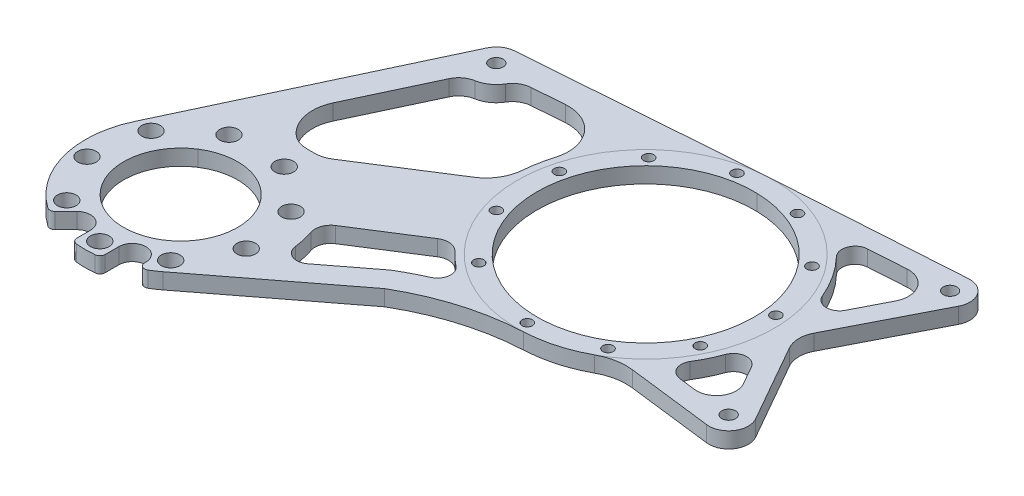
SolidWorks part; units mm, degrees
note: '?' marks a value the reader was unsure of.
other "Markup2"
sketch "Sketch8" plane through (392.176, 9.525, 205.994) normal (0, 1, 0) x (-1, 0, 0)
other "Markup3"
sketch "Sketch9" plane through (392.176, 9.525, 4.4528) normal (0, 1, 0) x (-1, 0, 0)
material "6061-T6 (SS)"
ref_plane "X-Y Datum" through (0, 0, 0) normal (0, 0, 1) x (1, 0, 0)
ref_plane "X-Z Datum" through (0, 0, 0) normal (0, 1, 0) x (1, 0, 0)
ref_plane "Y-Z Datum" through (0, 0, 0) normal (1, 0, 0) x (0, 0, -1)
sketch "Sketch1" plane through (0, 0, 0) normal (0, 1, 0) x (-1, 0, 0)
  line L1 (-575.31, 72.8215) -> (-438.15, 160.02) construction
  line L2 (-663.3443, 5.1159) -> (-571.3342, 11.0368)
  line L3 (-568.96, 0) -> (-463.042, 0) construction
  line L4 (-575.31, 72.8215) -> (-463.042, 0) construction
  line L6 (-672.4346, 18.9616) -> (-648.7868, 65.1568)
  line L8 (-414.9501, 197.3367) -> (-420.215, 192.0718)
  line L9 (-431.3112, 196.668) -> (-431.3112, 203.2407)
  line L10 (-444.9888, 203.2407) -> (-444.9888, 196.668)
  line L11 (-457.9888, 196.668) -> (-457.9888, 197.245)
  line L12 (-685.8, 0) -> (-568.96, 0) construction
  line L13 (-685.8, 130.5733) -> (-685.8, 0) construction
  line L16 (-450.7361, 24.8976) -> (-396.5254, 140.5006)
  line L17 (-670.601, 115.0847) -> (-649.0541, 77.2258)
  line L18 (-526.6297, 150.1211) -> (-466.1201, 196.5067)
  line L20 (-508.2633, 125.1657) -> (-498.3912, 109.6373) construction
  line L21 (-503.8626, 118.2436) -> (-490.7147, 118.2436) construction
  line L22 (-698.5, 155.9733) -> (-673.1, 155.9733) construction
  line L23 (-698.5, 12.7) -> (-673.1, 12.7) construction
  line L24 (-698.5, 12.7) -> (-698.5, -12.7) construction
  line L25 (-698.5, -12.7) -> (-673.1, -12.7) construction
  line L26 (-673.1, 12.7) -> (-673.1, -12.7) construction
  line L27 (-698.5, 12.7) -> (-673.1, -12.7) construction
  line L28 (-698.5, -12.7) -> (-673.1, 12.7) construction
  line L29 (-698.5, 155.9733) -> (-698.5, 130.5733) construction
  line L30 (-698.5, 130.5733) -> (-673.1, 130.5733) construction
  line L31 (-673.1, 155.9733) -> (-673.1, 130.5733) construction
  line L32 (-698.5, 155.9733) -> (-673.1, 130.5733) construction
  line L33 (-698.5, 130.5733) -> (-673.1, 155.9733) construction
  line L35 (-661.162, 129.2501) -> (-620.2745, 124.2297)
  line L36 (-672.139, 129.6123) -> (-652.5065, 109.9799) construction
  line L37 (-463.042, 0) -> (-463.042, 3.81) construction
  line L38 (-570.7022, 11.0807) -> (-458.6511, 19.4431)
  line L40 (-575.31, 125.209) -> (-575.31, 134.734) construction
  circle A3 centre (-438.15, 199.02) radius 4.5 construction
  circle A4 centre (-438.15, 160.02) radius 39 construction
  circle A5 centre (-662.3228, 119.7961) radius 9.525 construction
  circle A6 centre (-663.956, 14.6213) radius 9.525 construction
  circle A7 centre (-459.36, 28.9417) radius 9.525 construction
  circle A8 centre (-438.15, 160.02) radius 27.4955
  arc A11 (-411.6923, 197.6179) -> (-396.5254, 140.5006) centre (-438.15, 160.02) cw
  arc A13 (-672.4346, 18.9616) -> (-663.3443, 5.1159) centre (-663.956, 14.6213) ccw
  arc A16 (-461.8375, 199.4219) -> (-411.6923, 197.6179) centre (-438.15, 160.02) ccw construction
  arc A17 (-411.6923, 197.6179) -> (-414.9501, 197.3367) centre (-413.1541, 195.5407) ccw
  arc A18 (-431.3112, 196.668) -> (-420.215, 192.0718) centre (-424.8112, 196.668) ccw
  arc A19 (-431.3112, 203.2407) -> (-433.5998, 205.7683) centre (-433.8512, 203.2407) ccw
  arc A20 (-433.5998, 205.7683) -> (-442.7002, 205.7683) centre (-438.15, 160.02) ccw
  arc A21 (-442.7002, 205.7683) -> (-444.9888, 203.2407) centre (-442.4488, 203.2407) ccw
  arc A22 (-457.9888, 196.668) -> (-444.9888, 196.668) centre (-451.4888, 196.668) ccw
  arc A23 (-457.9888, 197.245) -> (-461.8375, 199.4219) centre (-460.5288, 197.245) ccw
  arc A25 (-466.1201, 196.5067) -> (-461.8375, 199.4219) centre (-438.15, 160.02) cw
  arc A27 (-526.6297, 150.1211) -> (-578.3125, 134.6611) centre (-583.7676, 247.0155) cw
  circle A38 centre (-575.31, 72.8215) radius 61.9125 construction
  circle A39 centre (-575.31, 72.8215) radius 52.3875
  arc A40 (-604.9989, 127.1513) -> (-578.3125, 134.6611) centre (-575.31, 72.8215) cw
  arc A41 (-670.601, 115.0847) -> (-661.162, 129.2501) centre (-662.3228, 119.7961) cw
  circle A42 centre (-662.3228, 119.7961) radius 3.3
  circle A43 centre (-663.956, 14.6213) radius 3.3
  circle A44 centre (-459.36, 28.9417) radius 3.3
  arc A47 (-649.0541, 77.2258) -> (-648.7868, 65.1568) centre (-660.0917, 70.9439) cw
  arc A49 (-620.2745, 124.2297) -> (-604.9989, 127.1513) centre (-617.179, 149.4404) ccw
  arc A51 (-450.7361, 24.8976) -> (-458.6511, 19.4431) centre (-459.36, 28.9417) cw
  circle A53 centre (-463.042, 3.81) radius 12.7 construction
  arc A54 (-571.3342, 11.0368) -> (-570.7022, 11.0807) centre (-575.31, 72.8215) ccw
  circle A55 centre (-685.8, 0) radius 12.7 construction
  circle A56 centre (-685.8, 1.6598) radius 12.7 construction
  circle A58 centre (-575.31, 129.9715) radius 2.5 construction
  point P71 (-685.8, 143.2733)
  point P103 (-662.3228, 119.7961)
  point P105 (-611.3847, 123.1382)
  point P112 (-611.3847, 123.1382)
  dimension "D5" = 25.4
  dimension "D6" = 685.8
  dimension "D7" = 123.825
  dimension "D8" = 104.775
  dimension "D9" = 5
  dimension "D13" = 45.974
  dimension "D14" = 19.05
  dimension "D15" = 3.81
  dimension "D16" = 117.8733
  dimension "D19" = 25.4
  dimension "D20" = 9
  dimension "D21" = 3.682
  dimension "D18" = 6.5
  dimension "D23" = 78
  dimension "D24" = 25.4
  dimension "D35" = 25.4
  dimension "D22" = 54.991
  dimension "D26" = 12.7
  dimension "D38" = 112.4868
  dimension "D41" = 6.6
  dimension "D42" = 32.446
  dimension "D43" = 21.844
  dimension "D34" = 38
  dimension "D36" = 1.6598
  dimension "D2" = 222.758
  dimension "D3" = 247.65
  dimension "D4" = 160.02
  dimension "D10" = 575.31
  dimension "D11" = 72.8215
  dimension "D12" = 116.84
  dimension "D17" = 25.4
  dimension "D25" = 22.3788
  dimension "D33" = 15.354
  dimension "D37" = 25.4
  dimension "D39" = 9.8989
  dimension "D40" = 88.4797
  dimension "D44" = 72.8215
  dimension "D46" = 10.7772
  dimension "D47" = 10.7772
extrude "Boss-Extrude1" add sketch "Sketch1" along normal mid plane 7.62
hole_wizard "M8 Clearance Hole1" positions "Sketch5" profile "Sketch4" hole size "M8" standard "ANSI Metric" end condition through all
sketch "Sketch5" plane through (0, -3.81, 0) normal (0, -1, 0) x (-1, 0, 0)
  point P0 (-438.15, -199.02)
sketch "Sketch4" plane through (438.15, -3.81, 199.02) normal (1, 0, 0) x (0, 0, -1)
  line L0 (0, 0) -> (0, 7.62)
  line L1 (0, 7.62) -> (4.5, 7.62)
  line L2 (4.5, 7.62) -> (4.5, 0.025)
  line L3 (4.5, 0.025) -> (4.525, 0)
  line L5 (4.525, 0) -> (0, 0)
  line L6 (-4.5, 0.025) -> (-4.525, 0) construction
  line L11 (0, -6.35) -> (0, 107.95) construction
  dimension "Thru Hole Dia." = 9
  dimension "Thru Hole Depth" = 7.62
  dimension "Near C'Sink Dia." = 9.05
  dimension "Near C'Sink Angle" = 90
pattern_circular "CirPattern1" count 9 over 360 about axis through (438.15, 0, 160.02) along (0, 1, 0) of "M8 Clearance Hole1"
sketch "Sketch6" plane through (0, 3.81, 0) normal (0, 1, 0) x (1, 0, 0)
  circle A0 centre (575.31, -72.8215) radius 61.9125 construction
  circle A1 centre (575.31, -72.8215) radius 61.9125
split line "Split Line2"
ref_point "Point1"
ref_point "Point2"
ref_plane "Plane1" through (570.7022, 0, 11.0807) normal (-0.8439, 0, 0.5365) x (0.5365, 0, 0.8439)
ref_plane "Plane2" through (438.15, 0, 160.02) normal (-0.8439, 0, 0.5365) x (0.5365, 0, 0.8439)
split line "Split Line3"
split line "Split Line4"
ref_axis "Axis1" through (575.31, 3.81, 72.8215) along (0, -1, 0)?
ref_axis "Axis2" through (438.15, 6.1381, 160.02) along (0, -1, 0)?
sketch "Sketch10" plane through (0, -3.81, 0) normal (0, -1, 0) x (1, 0, 0)
  line L0 (460.0554, 108.4708) -> (501.6535, 82.0251)
  line L1 (488.447, 135.5686) -> (518.5458, 116.4335)
  line L2 (462.2346, 30.2897) -> (408.0239, 145.8927)
  line L3 (454.4908, 46.8032) -> (436.5907, 84.9748)
  line L4 (449.5579, 110.4533) -> (453.2418, 110.4533)
  line L5 (575.31, 72.8215) -> (438.15, 160.02) construction
  line L9 (571.6474, 23.7455) -> (459.5963, 32.1079)
  line L13 (493.2983, 29.5927) -> (477.7847, 30.7505)
  line L18 (621.4353, 114.7757) -> (662.3228, 119.7961)
  line L21 (635.4204, 116.4929) -> (643.5069, 117.4858)
  line L23 (662.3228, 119.7961) -> (640.7759, 81.9372)
  line L25 (459.3594, 187.6874) -> (520.3915, 140.9012)
  line L26 (497.6765, 158.3141) -> (520.3915, 140.9012)
  line L27 (652.9459, 103.3204) -> (647.8594, 94.3831)
  line L29 (663.956, 14.6213) -> (571.9458, 20.5421)
  line L30 (644.4387, 15.8772) -> (626.4578, 17.0343)
  line L32 (640.3082, 60.8165) -> (663.956, 14.6213)
  line L33 (646.8337, 48.0691) -> (655.0441, 32.0304)
  arc A2 (520.3915, 140.9012) -> (577.7736, 123.5617) centre (583.7676, 247.0155) ccw
  arc A3 (520.3915, 140.9012) -> (533.1241, 134.268) centre (583.7676, 247.0155) ccw
  arc A5 (528.0838, 117.6107) -> (518.5458, 116.4335) centre (522.6004, 122.8112) cw
  arc A8 (576.9868, 7.7556) -> (634.9392, 98.9125) centre (575.31, 72.8215) ccw
  arc A9 (634.9392, 98.9125) -> (576.9868, 7.7556) centre (575.31, 72.8215) ccw
  arc A10 (622.2829, 27.7667) -> (635.326, 47.633) centre (575.31, 72.8215) ccw
  arc A11 (534.5034, 123.5285) -> (528.0838, 117.6107) centre (575.31, 72.8215) ccw
  arc A15 (464.8252, 201.9791) -> (411.4748, 118.0609) centre (438.15, 160.02) ccw
  arc A16 (411.4748, 118.0609) -> (464.8252, 201.9791) centre (438.15, 160.02) ccw
  arc A18 (485.3303, 144.3309) -> (487.5094, 154.0385) centre (438.15, 160.02) ccw
  arc A23 (436.5907, 84.9748) -> (440.9969, 107.134) centre (453.8385, 93.0629) cw
  arc A24 (533.1241, 134.268) -> (534.5034, 123.5285) centre (530.5222, 128.4755) cw
  arc A25 (487.5094, 154.0385) -> (497.6765, 158.3141) centre (493.8133, 153.2745) cw
  arc A26 (485.3303, 144.3309) -> (488.447, 135.5686) centre (492.5016, 141.9463) ccw
  arc A28 (510.4195, 67.5045) -> (512.9593, 54.0749) centre (575.31, 72.8215) ccw
  arc A29 (501.6535, 82.0251) -> (510.4195, 67.5045) centre (491.4332, 65.9488) cw
  arc A33 (470.2935, 35.4031) -> (461.5056, 41.4592) centre (459.36, 28.9417) ccw
  arc A34 (454.4908, 46.8032) -> (461.5056, 41.4592) centre (463.1147, 50.8473) ccw
  arc A39 (460.0554, 108.4708) -> (453.2418, 110.4533) centre (453.2418, 97.7533) ccw
  arc A40 (440.9969, 107.134) -> (449.5579, 110.4533) centre (449.5579, 97.7533) cw
  arc A48 (636.3823, 95.3283) -> (630.7823, 106.8686) centre (575.31, 72.8215) ccw
  arc A49 (643.5069, 117.4858) -> (652.9459, 103.3204) centre (644.6677, 108.0318) cw
  arc A50 (644.4387, 15.8772) -> (655.0441, 32.0304) centre (645.1523, 26.9668) ccw
  arc A51 (646.8337, 48.0691) -> (635.326, 47.633) centre (641.1813, 45.1756) ccw
  arc A52 (622.2829, 27.7667) -> (626.4578, 17.0343) centre (626.8656, 23.3712) ccw
  arc A53 (647.8594, 94.3831) -> (636.3823, 95.3283) centre (642.3406, 97.5241) cw
  arc A54 (630.7823, 106.8686) -> (635.4204, 116.4929) centre (636.1943, 110.1902) cw
  arc A55 (493.2983, 29.5927) -> (512.9593, 54.0749) centre (494.716, 48.5899) ccw
  arc A56 (470.2935, 35.4031) -> (477.7847, 30.7505) centre (478.4936, 40.2491) ccw
  point P14 (664.5919, 13.9778)
  point P78 (663.9188, 4.4766)
  point P79 (466.5721, 18.457)
  point P81 (467.2452, 27.9582)
  point P82 (664.8163, 17.1448)
  point P83 (467.4696, 31.1253)
  point P84 (664.5919, 13.9778)
  point P85 (467.2452, 27.9582)
  point P90 (639.9456, 80.4782)
  dimension "D5" = 12.7
  dimension "D10" = 19.05
  dimension "D11" = 9.525
  dimension "D13" = 9.525
  dimension "D14" = 9.525
  dimension "D15" = 9.525
  dimension "D16" = 9.525
  dimension "D17" = 19.05
  dimension "D18" = 6.35
  dimension "D21" = 7.5574
  dimension "D22" = 12.7
  dimension "D23" = 19.05
  dimension "D24" = 11.1125
  dimension "D3" = 25.4
  dimension "D4" = 9.525
  dimension "D20" = 12.7
  dimension "D27" = 6.35
  dimension "D29" = 65.1079
  dimension "D12" = 9.525
  dimension "D26" = 6.35
  dimension "D9" = 12.7
  dimension "D19" = 6.35
  dimension "D25" = 38.1
  dimension "D6" = 11.1125
  dimension "D7" = 12.7
  dimension "D8" = 22.225
extrude "Cut-Extrude2" cut sketch "Sketch10" against normal through all
hole_wizard "Ø5.0mm Dowel Hole2" positions "Sketch13" profile "Sketch14" hole size "Ø5.0" standard "ANSI Metric"
sketch "Sketch13" plane through (0, 3.81, 0) normal (0, 1, 0) x (1, 0, 0)
  point P0 (575.31, -129.9715)
sketch "Sketch14" plane through (575.31, 3.81, 129.9715) normal (1, 0, 0) x (0, 0, 1)
  line L0 (0, 0) -> (0, 9.1222)
  line L1 (0, 9.1222) -> (2.5, 7.62)
  line L2 (2.5, 7.62) -> (2.5, 0)
  line L5 (2.5, 0) -> (0, 0)
  line L10 (0, 9.1222) -> (-2.5, 7.62) construction
  line L11 (0, -6.35) -> (0, 107.95) construction
  dimension "Hole Dia." = 5
  dimension "Hole Depth" = 7.62
  dimension "Drill Angle" = 118
pattern_circular "CirPattern3" count 11 every 32 about axis through (575.31, 0, 72.8215) along (0, 1, 0) of "Ø5.0mm Dowel Hole2"
